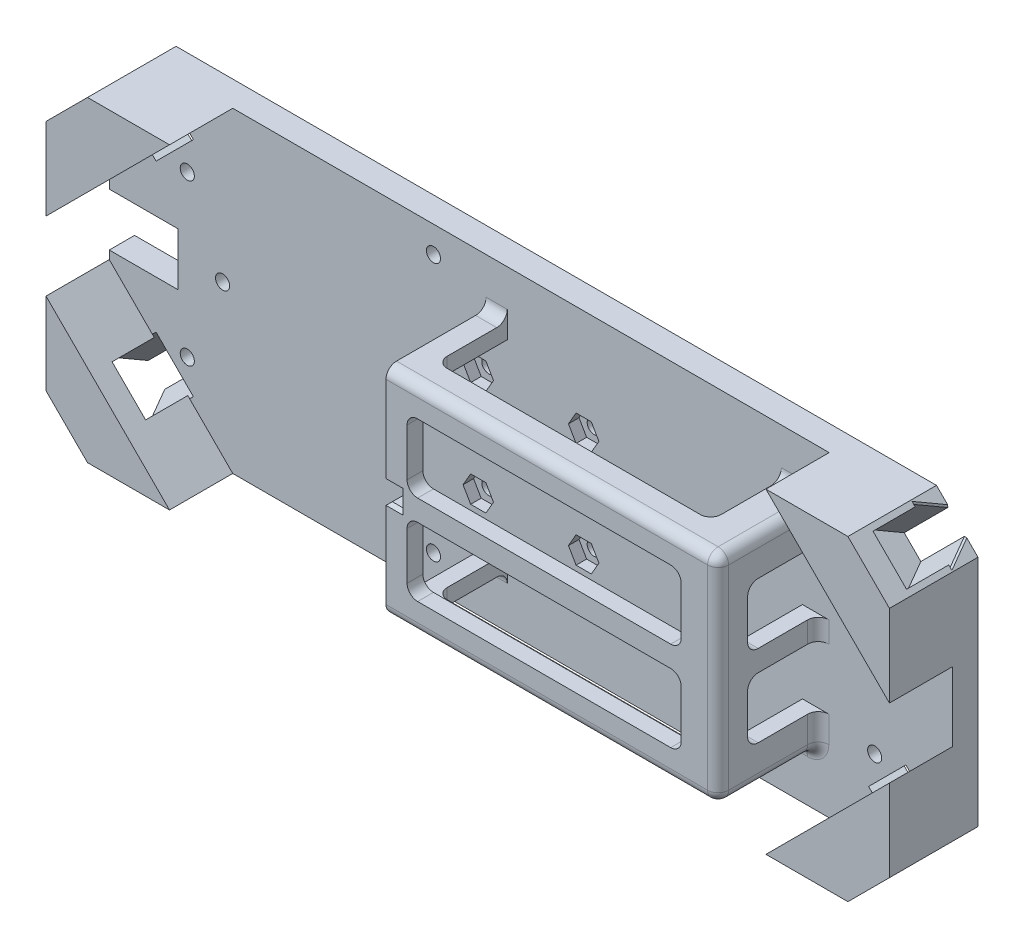
SolidWorks part; units mm, degrees
ref_plane "Front Plane" through (0, 0, 0) normal (0, 0, 1) x (1, 0, 0)
ref_plane "Top Plane" through (0, 0, 0) normal (0, 1, 0) x (1, 0, 0)
ref_plane "Right Plane" through (0, 0, 0) normal (1, 0, 0) x (0, 0, -1)
sketch "Sketch1" plane through (10.8587, 0, 0) normal (0, 0, 1) x (1, 0, 0)
  line L0 (-52.705, 21.59) -> (48.895, 21.59)
  line L1 (52.705, -25.4) -> (-52.705, -25.4)
  line L2 (52.705, -25.4) -> (52.705, 25.4)
  line L3 (52.705, 25.4) -> (-52.705, 25.4)
  line L4 (-52.705, -25.4) -> (-52.705, 25.4)
  line L5 (52.705, -25.4) -> (-52.705, 25.4) construction
  line L6 (52.705, 25.4) -> (-52.705, -25.4) construction
  line L7 (48.895, 21.59) -> (48.895, -22.86)
  line L8 (48.895, -22.86) -> (-52.705, -22.86)
  line L9 (-52.705, 13.97) -> (-6.985, 13.97)
  line L10 (-6.985, 13.97) -> (-6.985, -6.35)
  line L11 (-6.985, -6.35) -> (-52.705, -6.35)
  point P0 (0, 0)
  dimension "D1" = 105.41
  dimension "D2" = 50.8
  dimension "D3" = 101.6
  dimension "D4" = 44.45
  dimension "D5" = 3.81
  dimension "D6" = 45.72
  dimension "D7" = 20.32
  dimension "D8" = 7.62
extrude "Boss-Extrude1" add sketch "Sketch1" along normal blind 27.432 contours L7 L8 L4 L1 L2 L3 L0 region at (-40.6761, 23.495, 0)
extrude "Boss-Extrude2" add sketch "Sketch1<3>" along normal blind 5.08 contours L10 L11 L4 L8 L7 L0 L9 region at (16.19, -1.7862, 0)
sketch "Sketch1<3>" plane through (10.8587, 0, 0) normal (0, 0, 1) x (1, 0, 0) same geometry as "Sketch1"
sketch "Sketch4" plane through (10.8587, 0, 5.08) normal (0, 0, 1) x (1, 0, 0)
  line L0 (-52.705, 21.59) -> (48.895, 21.59) construction
  line L1 (-44.7859, 21.59) -> (-47.9241, 21.59)
  line L2 (-47.9241, 21.59) -> (-49.4932, 18.8722)
  line L3 (-49.4932, 18.8722) -> (-47.9241, 16.1544)
  line L4 (-47.9241, 16.1544) -> (-44.7859, 16.1544)
  line L5 (-44.7859, 16.1544) -> (-43.2168, 18.8722)
  line L6 (-43.2168, 18.8722) -> (-44.7859, 21.59)
  line L7 (-52.705, 13.97) -> (-52.705, 21.59) construction
  line L8 (-13.3987, 22.7847) -> (-13.3987, -11.3368) construction
  line L9 (21.1266, 16.1544) -> (17.9884, 16.1544)
  line L10 (17.9884, 16.1544) -> (16.4193, 18.8722)
  line L11 (16.4193, 18.8722) -> (17.9884, 21.59)
  line L12 (17.9884, 21.59) -> (21.1266, 21.59)
  line L13 (21.1266, 21.59) -> (22.6958, 18.8722)
  line L14 (22.6958, 18.8722) -> (21.1266, 16.1544)
  line L15 (0, 0) -> (10.9329, 0) construction
  line L16 (22.6958, -18.8722) -> (21.1266, -16.1544)
  line L17 (21.1266, -21.59) -> (22.6958, -18.8722)
  line L18 (17.9884, -21.59) -> (21.1266, -21.59)
  line L19 (16.4193, -18.8722) -> (17.9884, -21.59)
  line L20 (17.9884, -16.1544) -> (16.4193, -18.8722)
  line L21 (21.1266, -16.1544) -> (17.9884, -16.1544)
  line L22 (-49.4932, -18.8722) -> (-47.9241, -16.1544)
  line L23 (-47.9241, -21.59) -> (-49.4932, -18.8722)
  line L24 (-43.2168, -18.8722) -> (-44.7859, -21.59)
  line L25 (-44.7859, -16.1544) -> (-43.2168, -18.8722)
  line L26 (-47.9241, -16.1544) -> (-44.7859, -16.1544)
  line L27 (-44.7859, -21.59) -> (-47.9241, -21.59)
  circle A0 centre (-46.355, 18.8722) radius 2.7178 construction
  circle A1 centre (-46.355, 18.8722) radius 1.524
  circle A2 centre (19.5575, 18.8722) radius 1.524
  circle A3 centre (-46.355, -18.8722) radius 1.524
  circle A4 centre (19.5575, -18.8722) radius 1.524
  dimension "D4" = 3.048
  dimension "D1" = 5.4356
  dimension "D2" = 6.35
  dimension "D3" = 2.54
extrude "Cut-Extrude1" cut sketch "Sketch4" against normal blind 2.286 contours L5 L6 L14 L2 L3 L4 A1 | L14 L13 L11 L10 L9 A2 | L26 L22 L23 L12 L24 L25 A3 | L16 L21 L20 L19 L12 L17 A4 region at (-33.2145, 20.1896, 5.08) region at (30.4163, 16.2374, 5.08) region at (32.698, -20.1896, 5.08) region at (-37.778, -17.5548, 5.08)
extrude "Cut-Extrude2" cut sketch "Sketch4<4>" against normal through all contours A1 | A2 | A3 | A4 region at (-35.4963, 18.8722, 5.08) region at (30.4163, 18.8722, 5.08) region at (-35.4963, -18.8722, 5.08) region at (30.4163, -18.8722, 5.08)
sketch "Sketch4<4>" plane through (10.8587, 0, 5.08) normal (0, 0, 1) x (1, 0, 0) same geometry as "Sketch4"
sketch "Sketch7" plane through (10.8587, 0, 27.432) normal (0, 0, 1) x (1, 0, 0)
  line L0 (0, 0) -> (-46.355, 0) construction
  line L1 (-52.705, 25.4) -> (52.705, 25.4)
  line L2 (-52.705, 25.4) -> (-52.705, 6.35)
  line L3 (-52.705, -25.4) -> (52.705, -25.4)
  line L4 (52.705, 25.4) -> (52.705, -25.4)
  line L5 (-52.705, 6.35) -> (-46.355, 6.35)
  line L7 (-52.705, -6.35) -> (-46.355, -6.35)
  line L8 (-46.355, 6.35) -> (-46.355, -6.35)
  line L9 (-52.705, -6.35) -> (-52.705, -25.4)
  line L10 (-28.575, 0) -> (-1035.3573, 0) construction
  point P11 (-46.355, 0)
  dimension "D1" = 12.7
  dimension "D2" = 6.35
extrude "Boss-Extrude3" add sketch "Sketch7" along normal blind 3.81
fillet "Fillet1" radius 2.54 5 edges at (10.8587, -25.4, 31.242) (63.5637, -25.4, 15.621) (63.5637, 0, 31.242) (63.5637, 25.4, 15.621) (10.8587, 25.4, 31.242)
chamfer "Chamfer3" distance 1.27 angle 45 9 edges at (-41.8463, 21.59, 16.256) (-41.8463, -22.86, 16.256) (-41.8463, 13.97, 27.432) (-41.8463, -14.605, 27.432) (-41.8463, -6.35, 29.337) (-38.6713, -6.35, 31.242) (-35.4963, 0, 31.242) (-38.6713, 6.35, 31.242) (-41.8463, 6.35, 29.337)
chamfer "Chamfer4" distance 0.254 angle 45 4 edges at (-33.9723, -18.8722, 0) (31.9403, -18.8722, 0) (-33.9723, 18.8722, 0) (31.9403, 18.8722, 0)
sketch "Sketch8" plane through (10.8587, 0, 5.08) normal (0, 0, 1) x (1, 0, 0)
  line L0 (-52.705, -7.62) -> (-52.705, -22.86) construction
  line L1 (48.895, 21.59) -> (-52.705, 21.59)
  line L2 (48.895, 21.59) -> (48.895, -22.86)
  line L3 (48.895, -22.86) -> (-52.705, -22.86)
  line L4 (-52.705, 21.59) -> (-52.705, -22.86)
  line L5 (48.895, -22.86) -> (-51.435, -22.86) construction
extrude "Cut-Extrude3" cut sketch "Sketch8" against normal up to surface (5.08 mm away) up to face at (-33.7183, -18.8722, 0)
chamfer "Chamfer5" distance 1.27 angle 45 2 edges at (-41.8463, -22.86, 2.54) (-41.8463, 21.59, 2.54)
sketch "Sketch9" plane through (10.8587, 0, 0) normal (0, 0, -1) x (-1, 0, 0)
  line L0 (-90.7413, 28.1) -> (-80.7413, 38.1)
  line L1 (-80.7413, -38.1) -> (102.4587, -38.1)
  line L2 (-90.7413, -28.1) -> (-90.7413, 28.1)
  line L3 (-80.7413, 38.1) -> (102.4587, 38.1)
  line L4 (112.4587, -28.1) -> (112.4587, 28.1)
  line L5 (-90.7413, -38.1) -> (112.4587, 38.1) construction
  line L6 (-90.7413, 38.1) -> (112.4587, -38.1) construction
  line L7 (-90.7413, -28.1) -> (-80.7413, -38.1)
  line L8 (102.4587, 38.1) -> (112.4587, 28.1)
  line L9 (102.4587, -38.1) -> (112.4587, -28.1)
  point P0 (10.8587, 0)
  dimension "D1" = 203.2
  dimension "D2" = 76.2
extrude "Boss-Extrude4" add sketch "Sketch9" along normal blind 6.096
fillet "Fillet2" radius 1.27 5 edges at (9.5887, -25.4, 0) (62.8198, -24.6561, 0) (63.5637, 0, 0) (62.8198, 24.6561, 0) (9.5887, 25.4, 0)
sketch "Sketch11" plane through (0, 0, 0) normal (0, 0, 1) x (1, 0, 0)
  line L0 (-101.6, 28.1) -> (-91.6, 38.1)
  line L1 (-91.6, 38.1) -> (-84.9257, 38.1)
  line L4 (-101.6, -28.1) -> (-101.6, 28.1) construction
  line L5 (-101.6, 21.4257) -> (-101.6, 28.1)
  line L6 (0, 0) -> (0, 53.0626) construction
  line L7 (-1000, 0) -> (0, 0) construction
  line L25 (-76.5885, 29.7628) -> (-93.2628, 13.0885)
  line L26 (-84.9257, 38.1) -> (-76.5885, 29.7628)
  line L28 (-101.6, 21.4257) -> (-93.2628, 13.0885)
  line L54 (0, -17.1831) -> (0, 17.1831) construction
  line L55 (84.9257, 38.1) -> (76.5885, 29.7628)
  line L56 (91.6, 38.1) -> (84.9257, 38.1)
  line L57 (101.6, 28.1) -> (91.6, 38.1)
  line L58 (101.6, 21.4257) -> (101.6, 28.1)
  line L59 (101.6, 21.4257) -> (93.2628, 13.0885)
  line L60 (76.5885, 29.7628) -> (93.2628, 13.0885)
  line L61 (17.1831, 0) -> (-17.1831, 0) construction
  line L62 (91.6, -38.1) -> (84.9257, -38.1)
  line L63 (101.6, -28.1) -> (91.6, -38.1)
  line L64 (101.6, -21.4257) -> (101.6, -28.1)
  line L65 (101.6, -21.4257) -> (93.2628, -13.0885)
  line L66 (76.5885, -29.7628) -> (93.2628, -13.0885)
  line L67 (84.9257, -38.1) -> (76.5885, -29.7628)
  line L68 (-84.9257, -38.1) -> (-76.5885, -29.7628)
  line L69 (-91.6, -38.1) -> (-84.9257, -38.1)
  line L70 (-101.6, -28.1) -> (-91.6, -38.1)
  line L71 (-101.6, -21.4257) -> (-101.6, -28.1)
  line L72 (-101.6, -21.4257) -> (-93.2628, -13.0885)
  line L73 (-76.5885, -29.7628) -> (-93.2628, -13.0885)
  dimension "D1" = 16.51
  dimension "D2" = 8.3372
extrude "Boss-Extrude5" [suppressed] add sketch "Sketch11" along normal blind 19.05
sketch "Sketch13" plane through (-64.85, 64.85, 0) normal (-0.7071, 0.7071, 0) x (0, 0, 1)
  line L0 (-6.096, -44.9013) -> (-6.096, -42.0708)
  line L1 (-6.096, -51.9723) -> (-6.096, -37.8302) construction
  line L2 (-6.096, -42.0708) -> (0, -38.5513)
  line L3 (0, -38.5513) -> (0, -51.2513)
  line L4 (0, -51.2513) -> (-6.096, -47.7318)
  line L5 (-6.096, -47.7318) -> (-6.096, -44.9013)
  dimension "D1" = 6.096
  dimension "D2" = 120
  dimension "D3" = 120
  dimension "D4" = 12.7
extrude "Cut-Extrude4" cut sketch "Sketch13" against normal blind 15.24
mirror "Mirror2" about plane through (0, 0, 0) normal (0, 1, 0) of "Cut-Extrude4"
mirror "Mirror3" about plane through (0, 0, 0) normal (1, 0, 0) of "Cut-Extrude4", "Mirror2"
chamfer "Chamfer7" distance 0.381 angle 45 8 edges at (99.8458, -29.8542, -3.048) (93.3542, -36.3458, -3.048) (93.3542, 36.3458, -3.048) (99.8458, 29.8542, -3.048) (-93.3542, 36.3458, -3.048) (-99.8458, 29.8542, -3.048) (-93.3542, -36.3458, -3.048) (-99.8458, -29.8542, -3.048)
sketch "Sketch17" [suppressed] plane through (0, 0, 19.05) normal (0, 0, 1) x (1, 0, 0)
  line L0 (-96.6, 33.1) -> (-92.1099, 37.5901)
  line L1 (-91.6, 38.1) -> (-101.6, 28.1) construction
  line L3 (20.6756, 0) -> (-20.6756, 0) construction
  line L6 (-80.4355, -25.9158) -> (-89.4158, -16.9355)
  line L8 (-101.0901, 28.6099) -> (-96.6, 33.1)
  line L10 (-92.1099, -37.5901) -> (-80.4355, -25.9158)
  line L30 (-92.1099, 37.5901) -> (-80.4355, 25.9158)
  line L31 (-93.2628, 13.0885) -> (-76.5885, 29.7628) construction
  line L32 (-80.4355, 25.9158) -> (-89.4158, 16.9355)
  line L33 (-89.4158, 16.9355) -> (-101.0901, 28.6099)
  line L34 (-96.6, -33.1) -> (-92.1099, -37.5901)
  line L35 (-101.0901, -28.6099) -> (-96.6, -33.1)
  line L36 (-89.4158, -16.9355) -> (-101.0901, -28.6099)
  line L37 (0, -20.6756) -> (0, 20.6756) construction
  line L38 (92.1099, -37.5901) -> (80.4355, -25.9158)
  line L39 (96.6, -33.1) -> (92.1099, -37.5901)
  line L40 (101.0901, -28.6099) -> (96.6, -33.1)
  line L41 (89.4158, -16.9355) -> (101.0901, -28.6099)
  line L42 (80.4355, -25.9158) -> (89.4158, -16.9355)
  line L43 (80.4355, 25.9158) -> (89.4158, 16.9355)
  line L44 (92.1099, 37.5901) -> (80.4355, 25.9158)
  line L45 (96.6, 33.1) -> (92.1099, 37.5901)
  line L46 (101.0901, 28.6099) -> (96.6, 33.1)
  line L47 (89.4158, 16.9355) -> (101.0901, 28.6099)
  dimension "D1" = 12.7
extrude "Cut-Extrude7" [suppressed] cut sketch "Sketch17" against normal blind 10.922
sketch "Sketch18" [suppressed] plane through (0, 0, 8.128) normal (0, 0, 1) x (1, 0, 0)
  line L0 (-92.1099, 37.5901) -> (-101.0901, 28.6099) construction
  line L1 (-80.4355, 25.9158) -> (-92.1099, 37.5901) construction
  circle A0 centre (-89.4158, 25.9158) radius 1.778
  dimension "D1" = 3.556
  dimension "D2" = 10.16
  dimension "D3" = 6.35
extrude "Cut-Extrude8" [suppressed] cut sketch "Sketch18" against normal up to surface (8.382 mm away)
mirror "Mirror6" [suppressed] about plane through (0, 0, 0) normal (0, 1, 0)
mirror "Mirror7" [suppressed] about plane through (0, 0, 0) normal (1, 0, 0)
sketch "Sketch19" plane through (0, 0, 31.242) normal (0, 0, 1) x (1, 0, 0)
  line L1 (-67.9348, -33.6729) -> (67.9348, -33.6729)
  line L2 (-67.9348, -33.6729) -> (-67.9348, 33.6729)
  line L3 (-67.9348, 33.6729) -> (67.9348, 33.6729)
  line L4 (67.9348, -33.6729) -> (67.9348, 33.6729)
  line L5 (-67.9348, -33.6729) -> (67.9348, 33.6729) construction
  line L6 (-67.9348, 33.6729) -> (67.9348, -33.6729) construction
  point P0 (0, 0)
extrude "Cut-Extrude9" cut sketch "Sketch19" against normal up to surface (31.242 mm away) up to face at (0, 0, 0)
sketch "Sketch20" plane through (0, 0, 0) normal (0, 0, 1) x (1, 0, 0)
  line L0 (65.405, 22.86) -> (65.405, -21.59)
  line L1 (65.405, -21.59) -> (-10.795, -21.59)
  line L2 (65.405, 22.86) -> (-10.795, 22.86)
  line L3 (-10.795, 22.86) -> (-10.795, 26.67)
  line L4 (-10.795, 26.67) -> (69.215, 26.67)
  line L5 (69.215, 26.67) -> (69.215, -25.4)
  line L6 (69.215, -25.4) -> (-10.795, -25.4)
  line L7 (-10.795, -25.4) -> (-10.795, -21.59)
  line L8 (101.6, 28.1) -> (101.6, -28.1) construction
  line L9 (91.6, -38.1) -> (-91.6, -38.1) construction
  dimension "D1" = 52.07
  dimension "D2" = 44.45
  dimension "D3" = 3.81
  dimension "D4" = 80.01
  dimension "D5" = 76.2
  dimension "D6" = 32.385
  dimension "D7" = 12.7
extrude "Boss-Extrude6" add sketch "Sketch20" along normal blind 20.32
sketch "Sketch21" plane through (0, 0, 20.32) normal (0, 0, 1) x (1, 0, 0)
  line L1 (-10.795, 26.67) -> (69.215, 26.67)
  line L2 (-10.795, 26.67) -> (-10.795, -25.4)
  line L3 (-10.795, -25.4) -> (69.215, -25.4)
  line L4 (69.215, 26.67) -> (69.215, -25.4)
extrude "Boss-Extrude7" add sketch "Sketch21" along normal blind 3.81
fillet "Fillet3" radius 2.54 8 edges at (29.21, 26.67, 0) (69.215, 0.635, 0) (29.21, 26.67, 24.13) (69.215, 26.67, 12.065) (69.215, 0.635, 24.13) (69.215, -25.4, 12.065) (29.21, -25.4, 0) (29.21, -25.4, 24.13)
chamfer "Chamfer8" distance 1.27 angle 45 3 edges at (-10.795, -21.59, 10.16) (-10.795, 22.86, 10.16) (-10.795, 0.635, 20.32)
chamfer "Chamfer9" [suppressed] distance 0.254 angle 45
sketch "Sketch22" [suppressed] plane through (0, 0, -0.254) normal (0, 0, -1) x (-1, 0, 0)
  line L0 (-91.6432, -38.0568) -> (-101.5568, -28.1432) construction
  line L1 (-85.0164, -25.9158) -> (-87.2161, -22.1058)
  line L2 (-87.2161, -22.1058) -> (-91.6155, -22.1058)
  line L3 (-91.6155, -22.1058) -> (-93.8152, -25.9158)
  line L4 (-93.8152, -25.9158) -> (-91.6155, -29.7258)
  line L5 (-91.6155, -29.7258) -> (-87.2161, -29.7258)
  line L6 (-87.2161, -29.7258) -> (-85.0164, -25.9158)
  circle A0 centre (-89.4158, -25.9158) radius 3.81 construction
  circle A1 centre (-89.4158, -25.9158) radius 1.778 construction
  dimension "D1" = 7.62
  dimension "D2" = 10.16
  dimension "D3" = 0
extrude "Cut-Extrude10" [suppressed] cut sketch "Sketch22" against normal blind 3.302
mirror "Mirror8" [suppressed] about plane through (0, 0, 0) normal (0, 1, 0)
mirror "Mirror9" [suppressed] about plane through (0, 0, 0) normal (1, 0, 0)
sketch "Sketch23" plane through (0, 0, 0) normal (0, 0, 1) x (1, 0, 0)
  line L16 (90.3138, -17.8336) -> (100.8207, -28.3405)
  line L18 (-91.6, -38.1) -> (91.6, -38.1)
  line L19 (100.8207, -28.3405) -> (101.4012, -28.2988)
  line L20 (100.8207, -28.3405) -> (101.4012, -28.2988)
  line L21 (101.4012, -28.2988) -> (101.6, -28.1)
  line L22 (101.6, -28.1) -> (101.6, 28.1)
  line L23 (101.4012, -28.2988) -> (101.6, -28.1)
  line L24 (101.6, 28.1) -> (101.4012, 28.2988)
  line L25 (101.6, 28.1) -> (101.4012, 28.2988)
  line L26 (91.6, 38.1) -> (-91.6, 38.1)
  line L27 (101.4012, 28.2988) -> (100.8207, 28.3405)
  line L28 (101.4012, 28.2988) -> (100.8207, 28.3405)
  line L29 (90.3138, -17.8336) -> (100.8207, -28.3405)
  line L30 (-101.6, 28.1) -> (-101.6, -28.1)
  line L34 (-91.6, -38.1) -> (91.6, -38.1)
  line L38 (101.6, -28.1) -> (101.6, 28.1)
  line L42 (91.6, 38.1) -> (-91.6, 38.1)
  line L46 (-101.6, 28.1) -> (-101.6, -28.1)
  line L56 (91.8405, 37.3207) -> (91.7988, 37.9012)
  line L57 (91.8405, 37.3207) -> (91.7988, 37.9012)
  line L58 (91.7988, 37.9012) -> (91.6, 38.1)
  line L59 (91.7988, 37.9012) -> (91.6, 38.1)
  line L60 (-91.6, 38.1) -> (-91.7988, 37.9012)
  line L61 (-91.6, 38.1) -> (-91.7988, 37.9012)
  line L62 (-91.7988, 37.9012) -> (-91.8405, 37.3207)
  line L63 (-91.7988, 37.9012) -> (-91.8405, 37.3207)
  line L64 (100.8207, 28.3405) -> (90.3138, 17.8336)
  line L66 (-100.8207, 28.3405) -> (-101.4012, 28.2988)
  line L67 (-100.8207, 28.3405) -> (-101.4012, 28.2988)
  line L68 (-101.4012, 28.2988) -> (-101.6, 28.1)
  line L69 (-101.4012, 28.2988) -> (-101.6, 28.1)
  line L70 (-101.6, -28.1) -> (-101.4012, -28.2988)
  line L71 (-101.6, -28.1) -> (-101.4012, -28.2988)
  line L72 (-101.4012, -28.2988) -> (-100.8207, -28.3405)
  line L73 (-101.4012, -28.2988) -> (-100.8207, -28.3405)
  line L74 (100.8207, 28.3405) -> (90.3138, 17.8336)
  line L76 (-91.8405, -37.3207) -> (-91.7988, -37.9012)
  line L77 (-91.8405, -37.3207) -> (-91.7988, -37.9012)
  line L78 (-91.7988, -37.9012) -> (-91.6, -38.1)
  line L79 (-91.7988, -37.9012) -> (-91.6, -38.1)
  line L80 (91.6, -38.1) -> (91.7988, -37.9012)
  line L81 (91.6, -38.1) -> (91.7988, -37.9012)
  line L82 (91.7988, -37.9012) -> (91.8405, -37.3207)
  line L83 (91.7988, -37.9012) -> (91.8405, -37.3207)
  line L92 (90.3138, 17.8336) -> (81.3336, 26.8138)
  line L93 (90.3138, 17.8336) -> (81.3336, 26.8138)
  line L94 (81.3336, 26.8138) -> (91.8405, 37.3207)
  line L95 (81.3336, 26.8138) -> (91.8405, 37.3207)
  line L96 (-91.8405, 37.3207) -> (-81.3336, 26.8138)
  line L97 (-91.8405, 37.3207) -> (-81.3336, 26.8138)
  line L98 (-81.3336, 26.8138) -> (-90.3138, 17.8336)
  line L99 (-81.3336, 26.8138) -> (-90.3138, 17.8336)
  line L100 (-90.3138, 17.8336) -> (-100.8207, 28.3405)
  line L101 (-90.3138, 17.8336) -> (-100.8207, 28.3405)
  line L102 (-100.8207, -28.3405) -> (-90.3138, -17.8336)
  line L103 (-100.8207, -28.3405) -> (-90.3138, -17.8336)
  line L104 (-90.3138, -17.8336) -> (-81.3336, -26.8138)
  line L105 (-90.3138, -17.8336) -> (-81.3336, -26.8138)
  line L106 (-81.3336, -26.8138) -> (-91.8405, -37.3207)
  line L107 (-81.3336, -26.8138) -> (-91.8405, -37.3207)
  line L108 (91.8405, -37.3207) -> (81.3336, -26.8138)
  line L109 (91.8405, -37.3207) -> (81.3336, -26.8138)
  line L110 (81.3336, -26.8138) -> (90.3138, -17.8336)
  line L111 (81.3336, -26.8138) -> (90.3138, -17.8336)
  dimension "D1" = 0
sketch "Sketch24" plane through (0, 0, 0) normal (0, 0, 1) x (1, 0, 0)
  line L10 (-90.7628, 19.1806) -> (-101.6, 8.3434)
  line L11 (-101.6, -28.1) -> (-101.6, 28.1) construction
  line L12 (-101.6, 8.3434) -> (-101.6, 28.1)
  line L13 (-101.6, 28.1) -> (-100.6411, 29.0589)
  line L14 (-100.6411, 29.0589) -> (-90.7628, 19.1806)
  line L15 (-92.5589, 37.1411) -> (-91.6, 38.1)
  line L16 (-91.6, 38.1) -> (-71.8434, 38.1)
  line L17 (-91.6, 38.1) -> (91.6, 38.1) construction
  line L18 (-71.8434, 38.1) -> (-82.6806, 27.2628)
  line L19 (-82.6806, 27.2628) -> (-92.5589, 37.1411)
extrude "Boss-Extrude8" add sketch "Sketch24" along normal blind 10.16
sketch "Sketch26" plane through (0, 0, 10.16) normal (0, 0, 1) x (1, 0, 0)
  line L0 (-101.6, 8.3434) -> (-71.8434, 38.1)
  line L1 (-71.8434, 38.1) -> (-91.6, 38.1)
  line L2 (-91.6, 38.1) -> (-101.6, 28.1)
  line L3 (-101.6, 28.1) -> (-101.6, 8.3434)
extrude "Boss-Extrude10" add sketch "Sketch26" along normal blind 5.08
mirror "Mirror12" about plane through (0, 0, 0) normal (0, 1, 0) of "Boss-Extrude8", "Boss-Extrude10"
mirror "Mirror13" about plane through (0, 0, 0) normal (1, 0, 0) of "Mirror12"
sketch "Sketch27" plane through (0, 0, 0) normal (0, 0, 1) x (1, 0, 0)
  circle A0 centre (-23.495, 31.75) radius 1.7
  circle A1 centre (-23.495, -30.48) radius 1.7
extrude "Cut-Extrude11" cut sketch "Sketch27" against normal up to next
sketch "Sketch28" plane through (0, 0, -6.096) normal (0, 0, -1) x (-1, 0, 0)
  circle A0 centre (23.495, -30.48) radius 3.302
  circle A1 centre (23.495, 31.75) radius 3.302
  dimension "D1" = 6.604
extrude "Cut-Extrude12" cut sketch "Sketch28" against normal blind 3.302
sketch "Sketch29" plane through (0, 0, 24.13) normal (0, 0, 1) x (1, 0, 0)
  line L0 (-10.795, 24.13) -> (-10.795, -22.86) construction
  line L1 (-5.715, 19.685) -> (60.325, 19.685)
  line L2 (-5.715, 19.685) -> (-5.715, 3.175)
  line L3 (-5.715, -18.415) -> (60.325, -18.415)
  line L4 (60.325, 19.685) -> (60.325, 3.175)
  line L6 (66.675, -22.86) -> (66.675, 24.13) construction
  line L7 (-10.795, -22.86) -> (66.675, -22.86) construction
  line L8 (-5.715, -1.905) -> (-5.715, -18.415)
  line L9 (-5.715, 3.175) -> (60.325, 3.175)
  line L11 (-5.715, -1.905) -> (60.325, -1.905)
  line L13 (60.325, -1.905) -> (60.325, -18.415)
  dimension "D1" = 38.1
  dimension "D2" = 6.35
  dimension "D3" = 5.08
  dimension "D4" = 4.445
  dimension "D5" = 5.08
extrude "Cut-Extrude13" cut sketch "Sketch29" against normal up to next
sketch "Sketch30" plane through (0, -25.4, 0) normal (0, -1, 0) x (1, 0, 0)
  line L0 (71.8434, 0) -> (-71.8434, 0) construction
  line L1 (-5.715, 0) -> (60.325, 0)
  line L2 (-5.715, 0) -> (-5.715, 17.018)
  line L3 (-5.715, 17.018) -> (60.325, 17.018)
  line L4 (60.325, 0) -> (60.325, 17.018)
  line L5 (-10.795, 21.59) -> (-10.795, 2.54) construction
  line L6 (66.675, 2.54) -> (66.675, 21.59) construction
  line L7 (66.675, 21.59) -> (-10.795, 21.59) construction
  dimension "D1" = 5.08
  dimension "D2" = 6.35
  dimension "D3" = 4.572
extrude "Cut-Extrude14" cut sketch "Sketch30" against normal through all
sketch "Sketch31" plane through (69.215, 0, 0) normal (1, 0, 0) x (0, 0, -1)
  line L0 (-21.59, 24.13) -> (-21.59, -22.86) construction
  line L1 (-17.018, 17.78) -> (0, 17.78)
  line L2 (-17.018, 17.78) -> (-17.018, 3.175)
  line L3 (-17.018, -16.51) -> (0, -16.51)
  line L4 (0, 17.78) -> (0, 3.175)
  line L5 (0, 8.3434) -> (0, -8.3434) construction
  line L6 (-2.54, 24.13) -> (-21.59, 24.13) construction
  line L7 (-21.59, -22.86) -> (-2.54, -22.86) construction
  line L9 (-17.018, -1.905) -> (0, -1.905)
  line L11 (-17.018, 3.175) -> (0, 3.175)
  line L15 (-17.018, -1.905) -> (-17.018, -16.51)
  line L16 (0, -1.905) -> (0, -16.51)
  point P12 (-17.018, 0.635)
  dimension "D1" = 4.572
  dimension "D2" = 0
  dimension "D3" = 6.35
  dimension "D4" = 6.35
  dimension "D5" = 5.08
extrude "Cut-Extrude15" cut sketch "Sketch31" against normal up to next
sketch "Sketch32" plane through (0, -25.4, 0) normal (0, 1, 0) x (1, 0, 0)
  line L1 (-5.715, 0) -> (60.325, 0)
  line L2 (-5.715, 0) -> (-5.715, -2.54)
  line L3 (-5.715, -2.54) -> (60.325, -2.54)
  line L4 (60.325, 0) -> (60.325, -2.54)
extrude "Cut-Extrude16" cut sketch "Sketch32" against normal through all
sketch "Sketch33" plane through (69.215, 0, 0) normal (-1, 0, 0) x (0, 0, 1)
  line L0 (17.018, 17.78) -> (0, 17.78) construction
  line L1 (2.6099, 17.78) -> (0, 17.78)
  line L2 (2.6099, 17.78) -> (2.6099, -16.51)
  line L3 (2.6099, -16.51) -> (0, -16.51)
  line L4 (0, 17.78) -> (0, -16.51)
  line L5 (0, -16.51) -> (17.018, -16.51) construction
  point P6 (1.3049, -16.51)
  dimension "D1" = 0
  dimension "D2" = 0
extrude "Cut-Extrude17" cut sketch "Sketch33" against normal blind 3.302
sketch "Sketch34" plane through (0, 0, 0) normal (0, 0, 1) x (1, 0, 0)
  circle A0 centre (-74.295, 0.635) radius 1.7
extrude "Cut-Extrude18" cut sketch "Sketch34" against normal through all
sketch "Sketch35" plane through (0, 0, -6.096) normal (0, 0, -1) x (-1, 0, 0)
  circle A0 centre (74.295, 0.635) radius 3.302
  dimension "D1" = 6.604
extrude "Cut-Extrude19" cut sketch "Sketch35" against normal blind 3.302
fillet "Fillet4" radius 2.54 17 edges at (-5.715, 3.175, 22.225) (-5.715, -18.415, 22.225) (60.325, 3.175, 22.225) (60.325, -18.415, 22.225) (60.325, -1.905, 22.225) (60.325, 19.685, 22.225) (-5.715, 19.685, 22.225) (-5.715, -1.905, 22.225) (-5.715, -23.495, 17.018) (60.325, -23.495, 17.018) (-5.715, 24.765, 17.018) (60.325, 24.765, 17.018) (67.31, -16.51, 17.018) (67.31, 3.175, 17.018) (67.31, 17.78, 17.018) (67.31, -1.905, 17.018) (69.215, 0.635, 0)
hole_wizard "CBORE for M3 SHCS1" positions "Sketch36" profile "Sketch37" counterbore size "M3" standard "ANSI Metric" end condition up to next
sketch "Sketch36" plane through (0, 0, -6.096) normal (0, 0, -1) x (-1, 0, 0)
  line L0 (-91.6, -38.1) -> (91.6, -38.1) construction
  line L1 (101.6, -28.1) -> (101.6, 28.1) construction
  point P0 (82.804, -19.304)
  dimension "D1" = 18.796
  dimension "D2" = 18.796
sketch "Sketch37" plane through (-82.804, -19.304, -6.096) normal (1, 0, 0) x (0, 1, 0)
  line L0 (0, 0) -> (0, 6.097)
  line L1 (0, 6.097) -> (1.7, 6.097)
  line L3 (1.7, 6.097) -> (1.7, 3)
  line L4 (1.7, 3) -> (3.25, 3)
  line L5 (3.25, 3) -> (3.25, 0)
  line L7 (3.25, 0) -> (0, 0)
  line L11 (0, -6.35) -> (0, 107.95) construction
  dimension "Thru Hole Dia." = 3.4
  dimension "Thru Hole Depth" = 6.097
  dimension "C'Bore Dia." = 6.5
  dimension "C'Bore Depth" = 3
mirror "Mirror14" about plane through (0, 0, 0) normal (0, 1, 0) of "CBORE for M3 SHCS1"
mirror "Mirror15" about plane through (0, 0, 0) normal (1, 0, 0) of "Mirror14"
sketch "Sketch38" plane through (0, 0, -6.096) normal (0, 0, -1) x (-1, 0, 0)
  line L1 (-5.715, -3.81) -> (5.715, -3.81)
  line L2 (-5.715, -3.81) -> (-5.715, 3.81)
  line L3 (-5.715, 3.81) -> (5.715, 3.81)
  line L4 (5.715, -3.81) -> (5.715, 3.81)
  line L5 (-5.715, -3.81) -> (5.715, 3.81) construction
  line L6 (-5.715, 3.81) -> (5.715, -3.81) construction
  point P0 (0, 0)
  dimension "D1" = 11.43
  dimension "D2" = 7.62
extrude "Cut-Extrude20" cut sketch "Sketch38" against normal up to next
chamfer "Chamfer10" distance 0.762 angle 45 4 edges at (0, -3.81, -6.096) (5.715, 0, -6.096) (0, 3.81, -6.096) (-5.715, 0, -6.096)
hole_wizard "M3 Clearance Hole1" positions "Sketch39" profile "Sketch40" hole size "M3" standard "ANSI Metric" end condition up to next
sketch "Sketch39" plane through (0, 0, -6.096) normal (0, 0, -1) x (-1, 0, 0)
  line L0 (16.6243, 0) -> (-16.6243, 0) construction
  line L2 (0, 16.6243) -> (0, -16.6243) construction
  point P0 (12.7, 12.7)
  dimension "D1" = 12.7
  dimension "D2" = 12.7
sketch "Sketch40" plane through (-12.7, 12.7, -6.096) normal (1, 0, 0) x (0, 1, 0)
  line L0 (0, 0) -> (0, 6.097)
  line L1 (0, 6.097) -> (1.7, 6.097)
  line L2 (1.7, 6.097) -> (1.7, 0)
  line L5 (1.7, 0) -> (0, 0)
  line L11 (0, -6.35) -> (0, 107.95) construction
  dimension "Thru Hole Dia." = 3.4
  dimension "Thru Hole Depth" = 6.097
mirror "Mirror16" about plane through (0, 0, 0) normal (0, 1, 0) of "M3 Clearance Hole1"
mirror "Mirror17" about plane through (0, 0, 0) normal (1, 0, 0) of "Mirror16"
sketch "Sketch42" plane through (0, 0, 0) normal (0, 0, 1) x (1, 0, 0)
  line L1 (16.3662, 12.7) -> (14.5331, 15.875)
  line L2 (14.5331, 15.875) -> (10.8669, 15.875)
  line L3 (10.8669, 15.875) -> (9.0338, 12.7)
  line L4 (9.0338, 12.7) -> (10.8669, 9.525)
  line L5 (10.8669, 9.525) -> (14.5331, 9.525)
  line L6 (14.5331, 9.525) -> (16.3662, 12.7)
  circle A0 centre (12.7, 12.7) radius 3.175 construction
  dimension "D1" = 6.35
extrude "Cut-Extrude21" cut sketch "Sketch42" against normal blind 2.54
mirror "Mirror18" about plane through (0, 0, 0) normal (1, 0, 0) of "Cut-Extrude21"
mirror "Mirror19" about plane through (0, 0, 0) normal (0, 1, 0) of "Mirror18"
sketch "Sketch43" plane through (0, 0, 24.13) normal (0, 0, 1) x (1, 0, 0)
  line L0 (-10.795, 24.13) -> (-10.795, -22.86) construction
  line L1 (-14.097, -1.397) -> (-7.493, -1.397)
  line L2 (-14.097, -1.397) -> (-14.097, 2.667)
  line L3 (-14.097, 2.667) -> (-7.493, 2.667)
  line L4 (-7.493, -1.397) -> (-7.493, 2.667)
  line L5 (-14.097, -1.397) -> (-7.493, 2.667) construction
  line L6 (-14.097, 2.667) -> (-7.493, -1.397) construction
  point P0 (-10.795, 0.635)
  dimension "D1" = 6.604
  dimension "D2" = 4.064
extrude "Cut-Extrude22" cut sketch "Sketch43" against normal up to next
chamfer "Chamfer11" distance 0.762 angle 45 5 edges at (-10.795, -1.397, 22.86) (-9.144, -1.397, 24.13) (-7.493, 0.635, 24.13) (-9.144, 2.667, 24.13) (-10.795, 2.667, 22.86)
sketch "Sketch44" plane through (0, 0, 0) normal (0, 0, 1) x (1, 0, 0)
  line L0 (-101.6, -8.3434) -> (-101.6, 8.3434) construction
  line L1 (-118.142, -6.35) -> (-85.058, -6.35)
  line L2 (-118.142, -6.35) -> (-118.142, 6.35)
  line L3 (-118.142, 6.35) -> (-85.058, 6.35)
  line L4 (-85.058, -6.35) -> (-85.058, 6.35)
  line L5 (-118.142, -6.35) -> (-85.058, 6.35) construction
  line L6 (-118.142, 6.35) -> (-85.058, -6.35) construction
  point P0 (-101.6, 0)
  dimension "D1" = 12.7
extrude "Cut-Extrude23" cut sketch "Sketch44" against normal through all
